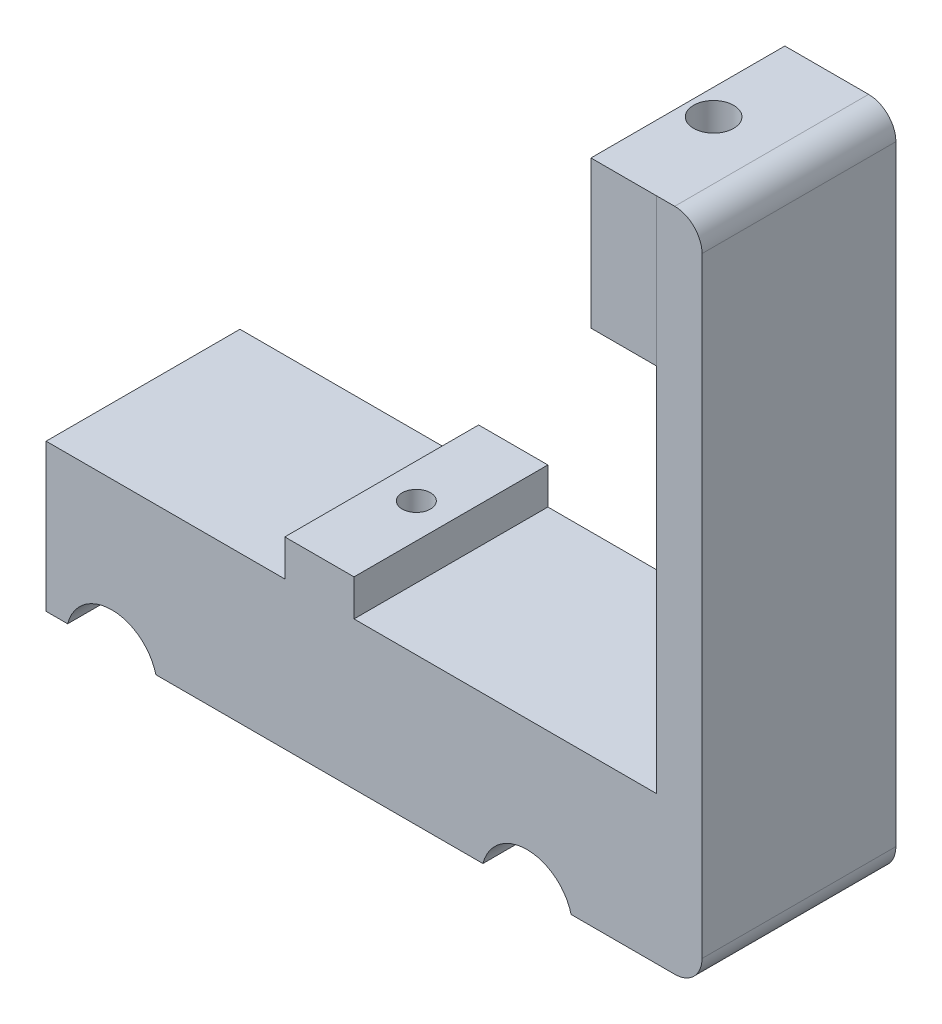
SolidWorks part; units mm, degrees
ref_plane "Front Plane" through (0, 0, 0) normal (0, 0, 1) x (1, 0, 0)
ref_plane "Top Plane" through (0, 0, 0) normal (0, 1, 0) x (1, 0, 0)
ref_plane "Right Plane" through (0, 0, 0) normal (1, 0, 0) x (0, 0, -1)
sketch "Sketch2" plane through (0, 0, 0) normal (0, 0, 1) x (1, 0, 0)
  line L0 (10.1, 0) -> (-10.1, 0)
  line L1 (-10.1, 0) -> (-10.1, 1.7099)
  line L2 (-10.1, 1.7099) -> (-6.2548, 7)
  line L3 (-6.2548, 7) -> (6.2548, 7)
  line L4 (0, 7) -> (0, 0)
  line L5 (0, 0) -> (0, 9.2516) construction
  line L6 (10.1, 1.7099) -> (6.2548, 7)
  line L7 (10.1, 0) -> (10.1, 1.7099)
  dimension "D1" = 20.2
  dimension "D2" = 7
extrude "Boss-Extrude1" add sketch "Sketch2" along normal blind 10.8 contours L4 L3 L2 L1 L0 | L0 L7 L6 L3 L4 region at (4.4168, 3.2082, 0) region at (-4.4168, 3.2082, 0)
sketch "Sketch4" plane through (0, 0, 0) normal (0, 0, 1) x (1, 0, 0)
  line L0 (-3.8, 0) -> (-3.8, -4.8)
  line L1 (10.1, 0) -> (-10.1, 0) construction
  line L2 (-3.8, -4.8) -> (-30, -4.8)
  line L3 (-30, -4.8) -> (-30, -29.8)
  line L4 (-30, -29.8) -> (30, -29.8)
  line L5 (0, 0) -> (0, -29.8) construction
  line L6 (0, -29.8) -> (0, 0)
  line L7 (3.8, 0) -> (-3.8, 0)
  line L8 (0, 0) -> (0, -30.5381) construction
  line L9 (30, -4.8) -> (30, -29.8)
  line L10 (3.8, -4.8) -> (30, -4.8)
  line L11 (3.8, 0) -> (3.8, -4.8)
  line L13 (-30, -20.98) -> (30, -20.98)
  line L14 (-30, -20.98) -> (-30, -23.48)
  line L15 (-30, -23.48) -> (30, -23.48)
  line L16 (30, -20.98) -> (30, -23.48)
  dimension "D1" = 4.8
  dimension "D2" = 3.8
  dimension "D3" = 25
  dimension "D4" = 60
  dimension "D6" = 8.82
extrude "Boss-Extrude2" add sketch "Sketch4" along normal mid plane 21.28 contours L6 L7 L0 L2 L3 L4 | L11 L7 L6 L4 L9 L10 region at (-14.5256, -12.5101, 0) region at (14.5256, -12.5101, 0)
sketch "Sketch5" plane through (0, 0, 0) normal (0, 0, 1) x (1, 0, 0)
  line L0 (-29.791, -22.2274) -> (26.9734, -22.2274) construction
  line L3 (0, -20.98) -> (0, 7) construction
  line L5 (-6.2548, 7) -> (6.2548, 7) construction
  line L20 (-30, -20.98) -> (30, -20.98) construction
  circle A0 centre (-22.791, -22.2274) radius 5
  circle A1 centre (22.791, -22.2274) radius 5
  dimension "D1" = 7
extrude "Cut-Extrude1" cut sketch "Sketch5" along normal through all both and the other way through all
fillet "Fillet1" radius 1 6 edges at (-10.1, 0, 5.4) (-10.1, 1.7099, 5.4) (-6.2548, 7, 5.4) (6.2548, 7, 5.4) (10.1, 0, 5.4) (10.1, 1.7099, 5.4)
sketch "Sketch6" plane through (30, 0, 0) normal (1, 0, 0) x (0, 0, -1)
  line L0 (-10.64, -20.98) -> (10.64, -20.98) construction
  line L1 (-10.64, -4.8) -> (10.64, -4.8)
  line L2 (-10.64, -4.8) -> (-10.64, -20.98)
  line L3 (-10.64, -20.98) -> (10.64, -20.98)
  line L4 (10.64, -4.8) -> (10.64, -20.98)
extrude "Boss-Extrude3" add sketch "Sketch6" along normal blind 12
sketch "Sketch7" plane through (0, -4.8, 0) normal (0, 1, 0) x (1, 0, 0)
  line L0 (3.8, -10.64) -> (42, -10.64) construction
  line L1 (42, 10.6413) -> (37, 10.6413)
  line L2 (42, 10.6413) -> (42, -10.64)
  line L3 (42, -10.64) -> (37, -10.64)
  line L4 (37, 10.6413) -> (37, -10.64)
  dimension "D1" = 5
extrude "Boss-Extrude4" add sketch "Sketch7" along normal blind 56.83
sketch "Sketch8" plane through (37, 0, 0) normal (-1, 0, 0) x (0, 0, 1)
  line L0 (-10.6413, 52.03) -> (-10.6413, -4.8) construction
  line L1 (10.643, 52.03) -> (-10.6413, 52.03)
  line L2 (10.643, 52.03) -> (10.643, 35.85)
  line L3 (10.643, 35.85) -> (-10.6413, 35.85)
  line L4 (-10.6413, 52.03) -> (-10.6413, 35.85)
  dimension "D1" = 16.18
extrude "Boss-Extrude5" add sketch "Sketch8" along normal blind 7.19
fillet "Fillet3" radius 3 2 edges at (42, 52.03, -0.0007) (42, -20.98, 0)
sketch "Sketch9" plane through (0, -20.98, 0) normal (0, -1, 0) x (1, 0, 0)
  line L0 (27.6329, 0) -> (27.6329, 10.8) construction
  line L2 (27.6329, 10.64) -> (39, 10.64) construction
  circle A0 centre (32.6329, 0) radius 2.2
  dimension "D1" = 5
  dimension "D2" = 10.64
extrude "Cut-Extrude2" cut sketch "Sketch9" against normal through all
sketch "Sketch10" plane through (0, -20.98, 0) normal (0, -1, 0) x (1, 0, 0)
  line L2 (-17.9491, 0) -> (-17.9491, 10.8) construction
  line L3 (-17.9491, 10.64) -> (17.9491, 10.64) construction
  circle A0 centre (0.0009, 0) radius 1.555
  dimension "D1" = 10.64
  dimension "D2" = 17.95
extrude "Cut-Extrude3" cut sketch "Sketch10" against normal through all
sketch "Sketch11" plane through (0, 0, 10.8) normal (0, 0, 1) x (1, 0, 0)
  line L0 (9.1, 0) -> (-9.1, 0) construction
  line L1 (-12.6098, 8.9215) -> (12.3675, 8.9215)
  line L2 (-12.6098, 8.9215) -> (-12.6098, -0.8)
  line L3 (-12.6098, -0.8) -> (12.3675, -0.8)
  line L4 (12.3675, 8.9215) -> (12.3675, -0.8)
  dimension "D1" = 0.8
extrude "Cut-Extrude4" cut sketch "Sketch11" against normal through all
